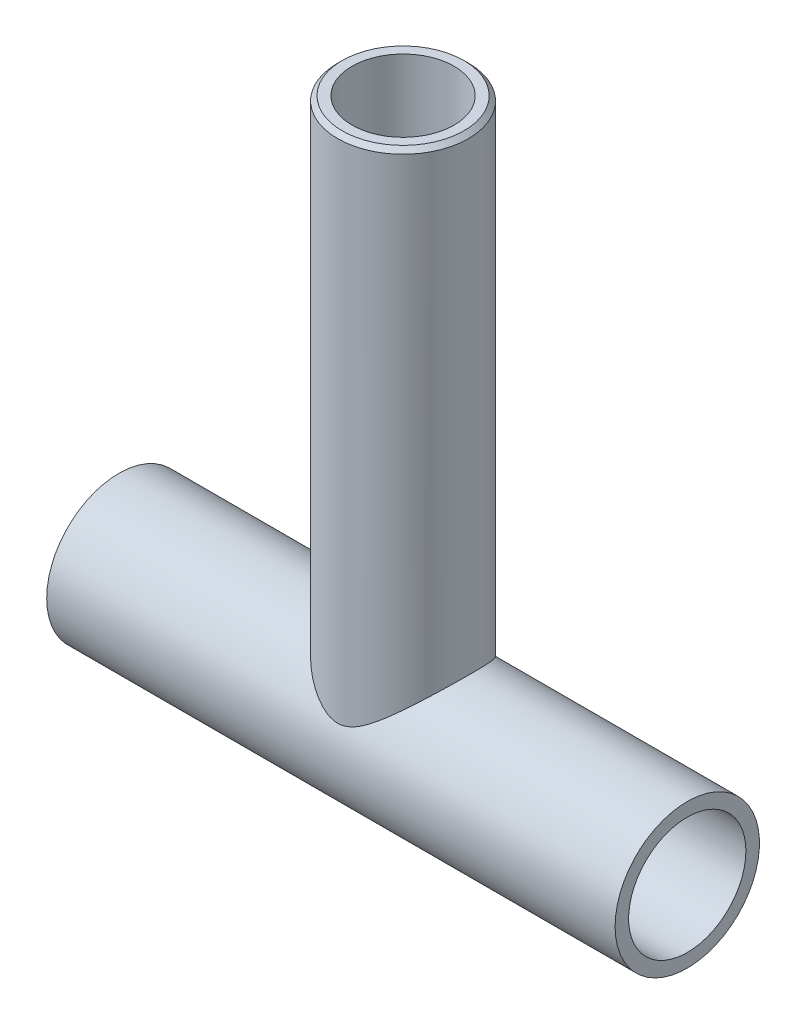
SolidWorks part; units mm, degrees
ref_plane "Front Plane" through (0, 0, 0) normal (0, 0, 1) x (1, 0, 0)
ref_plane "Top Plane" through (0, 0, 0) normal (0, 1, 0) x (1, 0, 0)
ref_plane "Right Plane" through (0, 0, 0) normal (1, 0, 0) x (0, 0, -1)
ref_plane "Plane1" through (0, 0, 0) normal (0, 0, -1) x (-1, 0, 0)
sketch "Sketch1" plane through (0, 0, 0) normal (0, 0, -1) x (-1, 0, 0)
  line L0 (-63, 16) -> (-63, 0)
  line L1 (-63, 0) -> (63, 0)
  line L2 (63, 0) -> (63, 16)
  line L3 (63, 16) -> (-63, 16)
  line L4 (-63, 0) -> (63, 0) construction
  dimension "D1" = 126
  dimension "D2" = 16
revolve "Revolve1" add sketch "Sketch1" angle 360 about L4 reverse direction yes
hole_wizard "M22 Clearance Hole1" positions "Sketch3" profile "Sketch2" hole size "M22" standard "ANSI Metric" end condition through all
sketch "Sketch3" plane through (63, 0, 0) normal (1, 0, 0) x (0, 0, -1)
  point P0 (0, 0)
sketch "Sketch2" plane through (63, 0, 0) normal (0, 1, 0) x (0, 0, -1)
  line L0 (0, 0) -> (0, 126)
  line L1 (0, 126) -> (13, 126)
  line L2 (13, 126) -> (13, 0)
  line L5 (13, 0) -> (0, 0)
  line L11 (0, -6.35) -> (0, 107.95) construction
  dimension "Thru Hole Dia." = 26
  dimension "Thru Hole Depth" = 126
ref_plane "Plane2" through (0, 120, 0) normal (0, 1, 0) x (1, 0, 0)
sketch "Sketch4" plane through (0, 120, 0) normal (0, 1, 0) x (1, 0, 0)
  circle A0 centre (0, 0) radius 14.5
extrude "Boss-Extrude1" add sketch "Sketch4" against normal up to next
ref_plane "Plane3" through (0, 18.5, 0) normal (0, 1, 0) x (1, 0, 0)
sketch "Sketch5" plane through (0, 18.5, 0) normal (0, 1, 0) x (1, 0, 0)
  circle A0 centre (0, 0) radius 13
extrude "Cut-Extrude1" cut sketch "Sketch5" against normal up to next
sketch "Sketch6" plane through (0, 18.5, 0) normal (0, -1, 0) x (1, 0, 0)
  circle A0 centre (0, 0) radius 9.0974
extrude "Cut-Extrude2" cut sketch "Sketch6" against normal blind 0.4 draft 70
sketch "Sketch7" plane through (0, 18.9, 0) normal (0, -1, 0) x (1, 0, 0)
  circle A0 centre (0, 0) radius 7.9984
extrude "Cut-Extrude3" cut sketch "Sketch7" against normal blind 1.26 draft 50 draft outward yes
sketch "Sketch8" plane through (0, 20.16, 0) normal (0, -1, 0) x (1, 0, 0)
  circle A0 centre (0, 0) radius 9.5
extrude "Cut-Extrude4" cut sketch "Sketch8" against normal blind 30.5245
sketch "Sketch9" plane through (0, 120, 0) normal (0, 1, 0) x (-1, 0, 0)
  circle A0 centre (0, 0) radius 11.3155
extrude "Cut-Extrude5" cut sketch "Sketch9" against normal blind 119.8155
chamfer "Chamfer1" distance 1 angle 45 1 edges at (0, 120, -14.5)
fillet "Fillet1" radius 3.2 1 edges at (0, 18.5, -13) tangent propagation no
